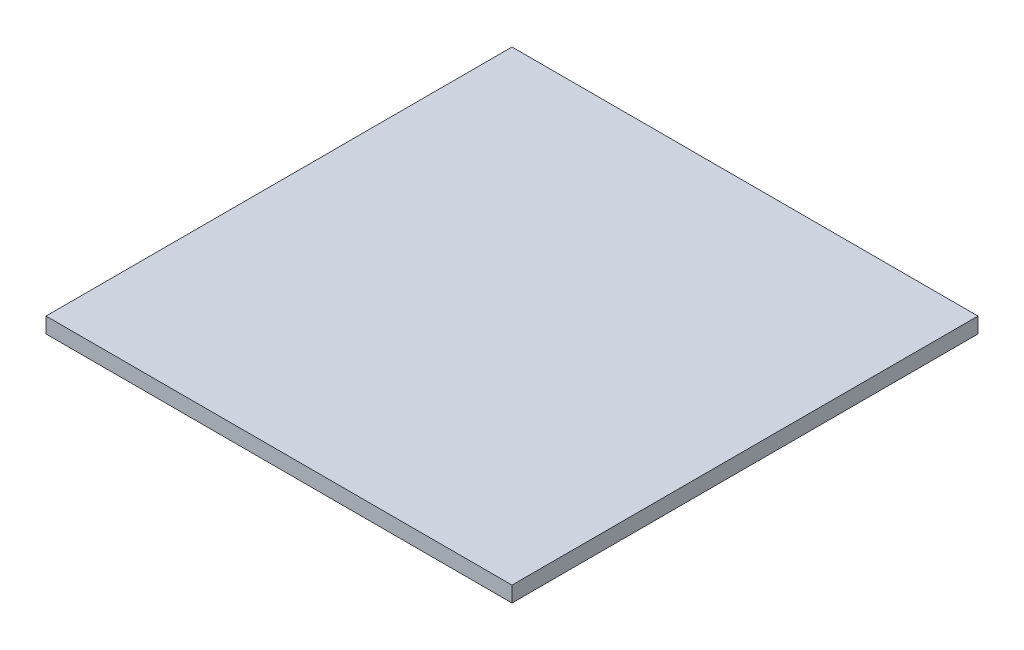
SolidWorks part; units mm, degrees
ref_plane "Front Plane" through (0, 0, 0) normal (0, 0, 1) x (1, 0, 0)
ref_plane "Top Plane" through (0, 0, 0) normal (0, 1, 0) x (1, 0, 0)
ref_plane "Right Plane" through (0, 0, 0) normal (1, 0, 0) x (0, 0, -1)
sketch "Sketch1" plane through (0, 0, 0) normal (0, 1, 0) x (1, 0, 0)
  line L1 (-150, -150) -> (150, -150)
  line L2 (-150, -150) -> (-150, 150)
  line L3 (-150, 150) -> (150, 150)
  line L4 (150, -150) -> (150, 150)
  line L5 (-150, -150) -> (150, 150) construction
  line L6 (-150, 150) -> (150, -150) construction
  point P0 (0, 0)
  dimension "D1" = 300
extrude "Boss-Extrude1" add sketch "Sketch1" along normal blind 10
